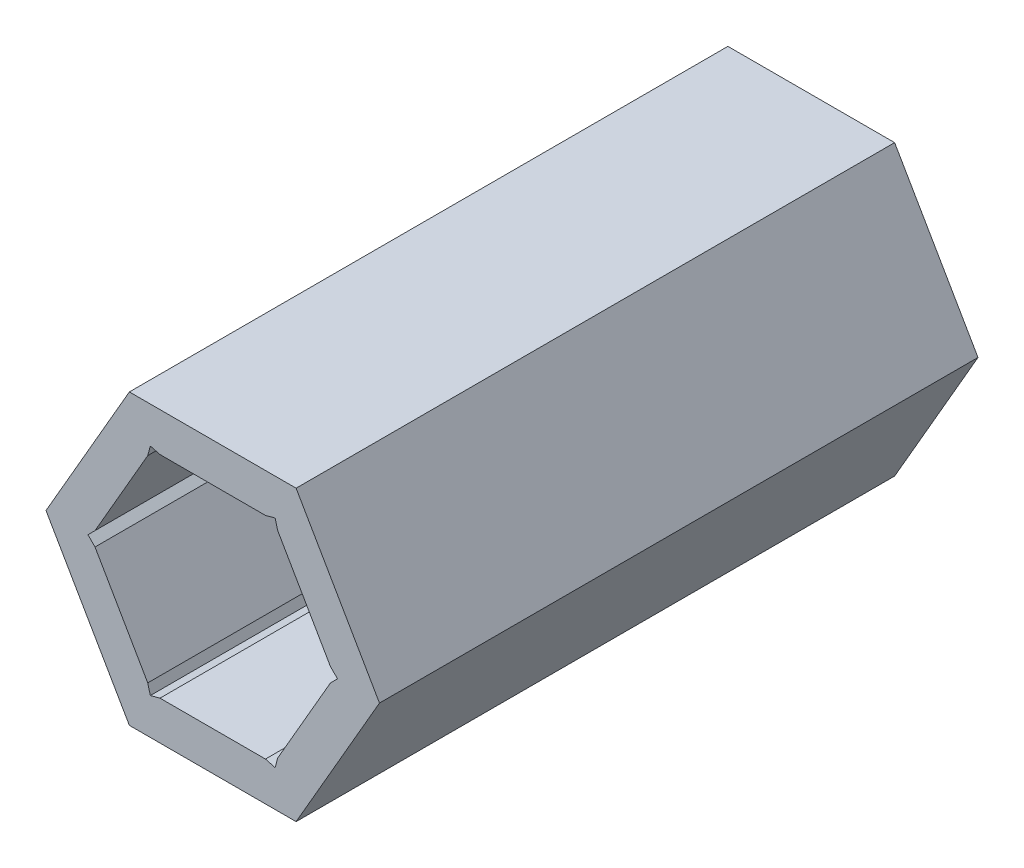
SolidWorks part; units mm, degrees
ref_plane "Piano frontale" through (0, 0, 0) normal (0, 0, 1) x (1, 0, 0)
ref_plane "Piano superiore" through (0, 0, 0) normal (0, 1, 0) x (1, 0, 0)
ref_plane "Piano destro" through (0, 0, 0) normal (1, 0, 0) x (0, 0, -1)
sketch "Hex-nut-botton" plane through (0, 0, 0) normal (0, 0, 1) x (1, 0, 0)
  line L0 (-4.0703, 7.05) -> (4.1703, -7.2232) construction
  line L1 (7.8674, 0.4732) -> (4.3435, 6.5768)
  line L2 (3.5239, 7.05) -> (-3.5239, 7.05)
  line L3 (-4.3435, 6.5768) -> (-7.8674, 0.4732)
  line L4 (-7.8674, -0.4732) -> (-4.3435, -6.5768)
  line L5 (-3.5239, -7.05) -> (3.5239, -7.05)
  line L6 (4.3435, -6.5768) -> (7.8674, -0.4732)
  line L7 (-4.0703, 7.05) -> (-4.1703, 7.2232) construction
  line L8 (-4.1703, 7.2232) -> (-3.5239, 7.05)
  line L9 (-4.1703, 7.2232) -> (-4.3435, 6.5768)
  line L10 (4.1703, 7.2232) -> (3.5239, 7.05)
  line L11 (4.1703, 7.2232) -> (4.3435, 6.5768)
  line L12 (8.3406, 0) -> (7.8674, 0.4732)
  line L13 (8.3406, 0) -> (7.8674, -0.4732)
  line L14 (4.1703, -7.2232) -> (4.3435, -6.5768)
  line L15 (4.1703, -7.2232) -> (3.5239, -7.05)
  line L16 (-4.1703, -7.2232) -> (-3.5239, -7.05)
  line L17 (-4.1703, -7.2232) -> (-4.3435, -6.5768)
  line L18 (-8.3406, 0) -> (-7.8674, -0.4732)
  line L19 (-8.3406, 0) -> (-7.8674, 0.4732)
  line L21 (11.1429, 0) -> (5.5714, 9.65)
  line L22 (5.5714, 9.65) -> (-5.5714, 9.65)
  line L23 (-5.5714, 9.65) -> (-11.1429, 0)
  line L24 (-11.1429, 0) -> (-5.5714, -9.65)
  line L25 (-5.5714, -9.65) -> (5.5714, -9.65)
  line L26 (5.5714, -9.65) -> (11.1429, 0)
  circle A0 centre (0, 0) radius 7.05 construction
  circle A1 centre (0, 0) radius 8.3406 construction
  circle A2 centre (0, 0) radius 9.65 construction
  point P29 (0, 0)
  dimension "D2" = 8.3406
  dimension "D1" = 14.1
  dimension "D3" = 45
  dimension "D4" = 6
  dimension "D5" = 2.6
extrude "Botton shaft" add sketch "Hex-nut-botton" along normal mid plane 6.5
sketch "Schizzo2" plane through (0, 0, 3.25) normal (0, 0, 1) x (1, 0, 0)
  line L0 (5.5714, 9.65) -> (-5.5714, 9.65) construction
  line L1 (-5.5714, 9.65) -> (-11.1429, 0) construction
  line L2 (11.1429, 0) -> (5.5714, 9.65) construction
  line L3 (5.5714, -9.65) -> (11.1429, 0) construction
  line L4 (-5.5714, -9.65) -> (5.5714, -9.65) construction
  line L5 (-11.1429, 0) -> (-5.5714, -9.65) construction
  line L6 (5.5714, 9.65) -> (-5.5714, 9.65)
  line L7 (-5.5714, 9.65) -> (-11.1429, 0)
  line L8 (11.1429, 0) -> (5.5714, 9.65)
  line L9 (5.5714, -9.65) -> (11.1429, 0)
  line L10 (-5.5714, -9.65) -> (5.5714, -9.65)
  line L11 (-11.1429, 0) -> (-5.5714, -9.65)
  circle A0 centre (0, 0) radius 4.5
  dimension "D1" = 9
extrude "Nut block" add sketch "Schizzo2" along normal blind 4
sketch "Hex-nut-top" plane through (0, 0, 7.25) normal (0, 0, 1) x (1, 0, 0)
  line L6 (11.1429, 0) -> (5.5714, 9.65)
  line L7 (5.5714, 9.65) -> (-5.5714, 9.65)
  line L8 (-5.5714, 9.65) -> (-11.1429, 0)
  line L9 (-11.1429, 0) -> (-5.5714, -9.65)
  line L10 (-5.5714, -9.65) -> (5.5714, -9.65)
  line L11 (5.5714, -9.65) -> (11.1429, 0)
  line L12 (11.1429, 0) -> (5.5714, 9.65)
  line L13 (5.5714, 9.65) -> (-5.5714, 9.65)
  line L14 (-5.5714, 9.65) -> (-11.1429, 0)
  line L15 (-11.1429, 0) -> (-5.5714, -9.65)
  line L16 (-5.5714, -9.65) -> (5.5714, -9.65)
  line L17 (5.5714, -9.65) -> (11.1429, 0)
  line L30 (7.8674, 0.4732) -> (4.3435, 6.5768)
  line L31 (4.3435, 6.5768) -> (4.1703, 7.2232)
  line L32 (4.1703, 7.2232) -> (3.5239, 7.05)
  line L33 (3.5239, 7.05) -> (-3.5239, 7.05)
  line L34 (-3.5239, 7.05) -> (-4.1703, 7.2232)
  line L35 (-4.1703, 7.2232) -> (-4.3435, 6.5768)
  line L36 (-4.3435, 6.5768) -> (-7.8674, 0.4732)
  line L37 (-7.8674, 0.4732) -> (-8.3406, 0)
  line L38 (-8.3406, 0) -> (-7.8674, -0.4732)
  line L39 (-7.8674, -0.4732) -> (-4.3435, -6.5768)
  line L40 (-4.3435, -6.5768) -> (-4.1703, -7.2232)
  line L41 (-4.1703, -7.2232) -> (-3.5239, -7.05)
  line L42 (-3.5239, -7.05) -> (3.5239, -7.05)
  line L43 (3.5239, -7.05) -> (4.1703, -7.2232)
  line L44 (4.1703, -7.2232) -> (4.3435, -6.5768)
  line L45 (4.3435, -6.5768) -> (7.8674, -0.4732)
  line L46 (7.8674, -0.4732) -> (8.3406, 0)
  line L47 (8.3406, 0) -> (7.8674, 0.4732)
  line L48 (7.8674, 0.4732) -> (4.3435, 6.5768)
  line L49 (4.3435, 6.5768) -> (4.1703, 7.2232)
  line L50 (4.1703, 7.2232) -> (3.5239, 7.05)
  line L51 (3.5239, 7.05) -> (-3.5239, 7.05)
  line L52 (-3.5239, 7.05) -> (-4.1703, 7.2232)
  line L53 (-4.1703, 7.2232) -> (-4.3435, 6.5768)
  line L54 (-4.3435, 6.5768) -> (-7.8674, 0.4732)
  line L55 (-7.8674, 0.4732) -> (-8.3406, 0)
  line L56 (-8.3406, 0) -> (-7.8674, -0.4732)
  line L57 (-7.8674, -0.4732) -> (-4.3435, -6.5768)
  line L58 (-4.3435, -6.5768) -> (-4.1703, -7.2232)
  line L59 (-4.1703, -7.2232) -> (-3.5239, -7.05)
  line L60 (-3.5239, -7.05) -> (3.5239, -7.05)
  line L61 (3.5239, -7.05) -> (4.1703, -7.2232)
  line L62 (4.1703, -7.2232) -> (4.3435, -6.5768)
  line L63 (4.3435, -6.5768) -> (7.8674, -0.4732)
  line L64 (7.8674, -0.4732) -> (8.3406, 0)
  line L65 (8.3406, 0) -> (7.8674, 0.4732)
  dimension "D1" = 0
  dimension "D2" = 0
extrude "Top shaft" add sketch "Hex-nut-top" along normal blind 29.5
ref_axis "vertical axis" through (0, 0, 7.25) along (0, 0, -1)
